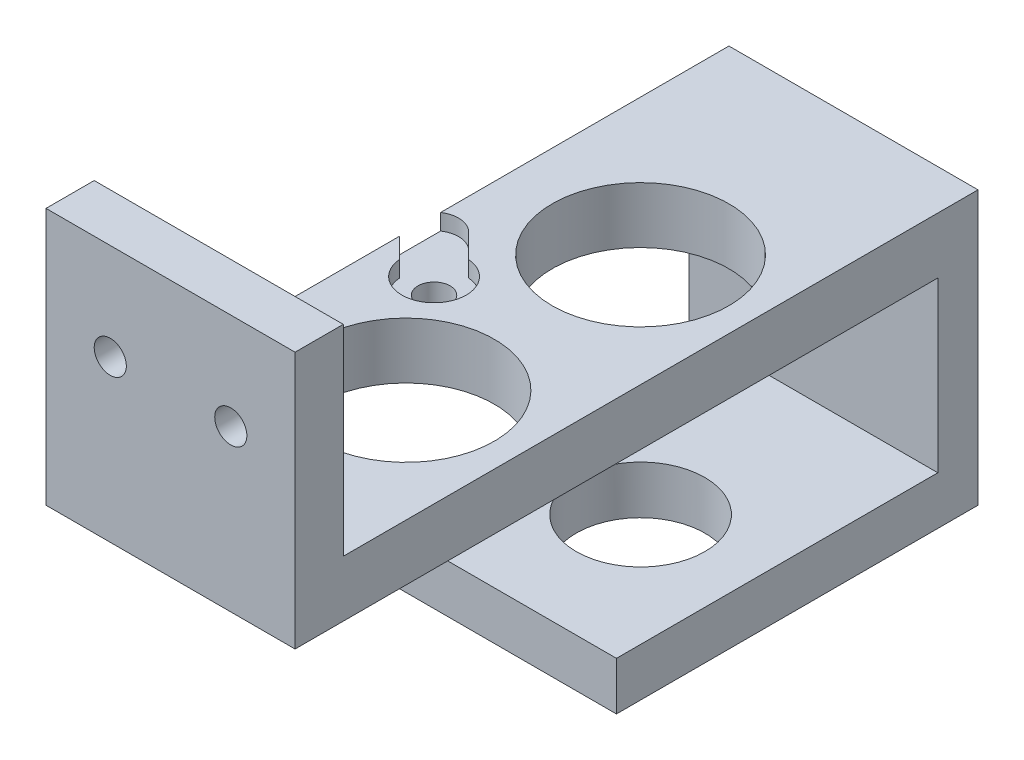
SolidWorks part; units mm, degrees
ref_plane "Front Plane" through (0, 0, 0) normal (0, 0, 1) x (1, 0, 0)
ref_plane "Top Plane" through (0, 0, 0) normal (0, 1, 0) x (1, 0, 0)
ref_plane "Right Plane" through (0, 0, 0) normal (1, 0, 0) x (0, 0, -1)
sketch "Sketch1" plane through (0, 0, 0) normal (0, 1, 0) x (1, 0, 0)
  line L1 (-50.1619, 28.7652) -> (-19.1619, 28.7652)
  line L2 (-50.1619, 28.7652) -> (-50.1619, -56.2348)
  line L3 (-50.1619, -56.2348) -> (-19.1619, -56.2348)
  line L4 (-19.1619, 28.7652) -> (-19.1619, -56.2348)
  dimension "D1" = 85
  dimension "D2" = 31
extrude "Boss-Extrude1" add sketch "Sketch1" along normal blind 7
sketch "Sketch2" plane through (0, 7, 0) normal (0, 1, 0) x (1, 0, 0)
  line L0 (-50.1619, -56.2348) -> (-19.1619, -56.2348) construction
  line L1 (-50.1619, 28.7652) -> (-50.1619, -56.2348) construction
  circle A0 centre (-33.1619, 0.7652) radius 11
  dimension "D1" = 22
  dimension "D2" = 57
  dimension "D3" = 17
extrude "Cut-Extrude1" cut sketch "Sketch2" against normal blind 100
sketch "Sketch3" plane through (0, 7, 0) normal (0, 1, 0) x (1, 0, 0)
  line L0 (-50.1619, 28.7652) -> (-50.1619, -56.2348) construction
  circle A0 centre (-33.1619, -28.4348) radius 11
  circle A1 centre (-33.1619, 0.7652) radius 11 construction
  dimension "D1" = 22
  dimension "D2" = 29.2
  dimension "D3" = 17
extrude "Cut-Extrude2" cut sketch "Sketch3" against normal blind 7
sketch "Sketch4" plane through (0, 7, 0) normal (0, 1, 0) x (1, 0, 0)
  line L0 (-19.1619, -56.2348) -> (-19.1619, 28.7652) construction
  line L1 (-50.1619, -56.2348) -> (-19.1619, -56.2348)
  line L2 (-50.1619, -56.2348) -> (-50.1619, -50.2348)
  line L3 (-50.1619, -50.2348) -> (-19.1619, -50.2348)
  line L4 (-19.1619, -56.2348) -> (-19.1619, -50.2348)
  dimension "D1" = 6
extrude "Boss-Extrude3" add sketch "Sketch4" along normal blind 25
sketch "Sketch5" plane through (0, 0, 50.2348) normal (0, 0, -1) x (-1, 0, 0)
  line L0 (50.1619, 32) -> (50.1619, 7) construction
  line L1 (19.1619, 32) -> (50.1619, 32) construction
  circle A0 centre (42.1619, 20) radius 2
  circle A1 centre (27.1619, 20) radius 2
  dimension "D1" = 4
  dimension "D2" = 4
  dimension "D3" = 8
  dimension "D4" = 15
  dimension "D5" = 0
  dimension "D6" = 12
extrude "Cut-Extrude3" cut sketch "Sketch5" against normal blind 14
sketch "Sketch6" plane through (0, 7, 0) normal (0, 1, 0) x (1, 0, 0)
  circle A0 centre (-43.6619, -14.4348) radius 2
  circle A1 centre (-43.6619, -42.4348) radius 2
  circle A2 centre (-33.1619, -28.4348) radius 11 construction
  dimension "D1" = 4
  dimension "D2" = 4
  dimension "D3" = 28
  dimension "D4" = 10.5
  dimension "D5" = 14
  dimension "D6" = 0
extrude "Cut-Extrude4" cut sketch "Sketch6" against normal blind 14
sketch "Sketch9" plane through (0, 7, 0) normal (0, 1, 0) x (1, 0, 0)
  circle A2 centre (-33.1619, 0.7652) radius 8
  circle A3 centre (-33.1619, 0.7652) radius 11 construction
  dimension "D1" = 16
  dimension "D2" = 0
sketch "Sketch10" plane through (0, 0, 0) normal (0, -1, 0) x (1, 0, 0)
  line L0 (-19.1619, 56.2348) -> (-19.1619, -28.7652) construction
  line L1 (-50.1619, -28.7652) -> (-19.1619, -28.7652)
  line L2 (-50.1619, -28.7652) -> (-50.1619, -23.7652)
  line L3 (-50.1619, -23.7652) -> (-19.1619, -23.7652)
  line L4 (-19.1619, -28.7652) -> (-19.1619, -23.7652)
  dimension "D1" = 5
extrude "Boss-Extrude4" add sketch "Sketch10" along normal blind 27
sketch "Sketch11" plane through (0, 0, -23.7652) normal (0, 0, 1) x (1, 0, 0)
  line L0 (-19.1619, -27) -> (-19.1619, 0) construction
  line L1 (-50.1619, -27) -> (-19.1619, -27)
  line L2 (-50.1619, -27) -> (-50.1619, -21)
  line L3 (-50.1619, -21) -> (-19.1619, -21)
  line L4 (-19.1619, -27) -> (-19.1619, -21)
  dimension "D1" = 6
extrude "Boss-Extrude5" add sketch "Sketch11" along normal blind 40
extrude "Cut-Extrude5" cut sketch "Sketch9" against normal blind 40
sketch "Sketch13" plane through (0, 7, 0) normal (0, 1, 0) x (1, 0, 0)
  circle A0 centre (-43.6619, -14.4348) radius 4
  circle A2 centre (-43.6619, -14.4348) radius 2 construction
  circle A3 centre (-43.6619, -42.4348) radius 4
  circle A4 centre (-43.6619, -42.4348) radius 2 construction
  circle A5 centre (-43.6619, -42.4348) radius 2 construction
  dimension "D1" = 0
  dimension "D2" = 8
  dimension "D3" = 0
  dimension "D4" = 0
  dimension "D5" = 8
extrude "Cut-Extrude6" cut sketch "Sketch13" against normal blind 2
sketch "Sketch15" plane through (0, 7, 0) normal (0, 1, 0) x (1, 0, 0)
  line L0 (-43.6619, -14.4348) -> (-48.4475, -9.6492) construction
  line L1 (-45.8193, -16.5922) -> (-50.6049, -11.8066)
  line L2 (-41.5046, -12.2775) -> (-46.2902, -7.4919)
  line L3 (-43.6619, -42.4348) -> (-48.8836, -47.6565) construction
  line L4 (-41.3168, -44.78) -> (-46.5384, -50.0016)
  line L5 (-46.0071, -40.0897) -> (-51.2288, -45.3113)
  arc A0 (-45.8193, -16.5922) -> (-41.5046, -12.2775) centre (-43.6619, -14.4348) ccw
  arc A1 (-46.2902, -7.4919) -> (-50.6049, -11.8066) centre (-48.4475, -9.6492) ccw
  arc A2 (-41.3168, -44.78) -> (-46.0071, -40.0897) centre (-43.6619, -42.4348) ccw
  arc A3 (-51.2288, -45.3113) -> (-46.5384, -50.0016) centre (-48.8836, -47.6565) ccw
  point P3 (-46.0547, -12.042)
  point P8 (-46.2728, -45.0456)
extrude "Cut-Extrude9" cut sketch "Sketch15" against normal blind 2
